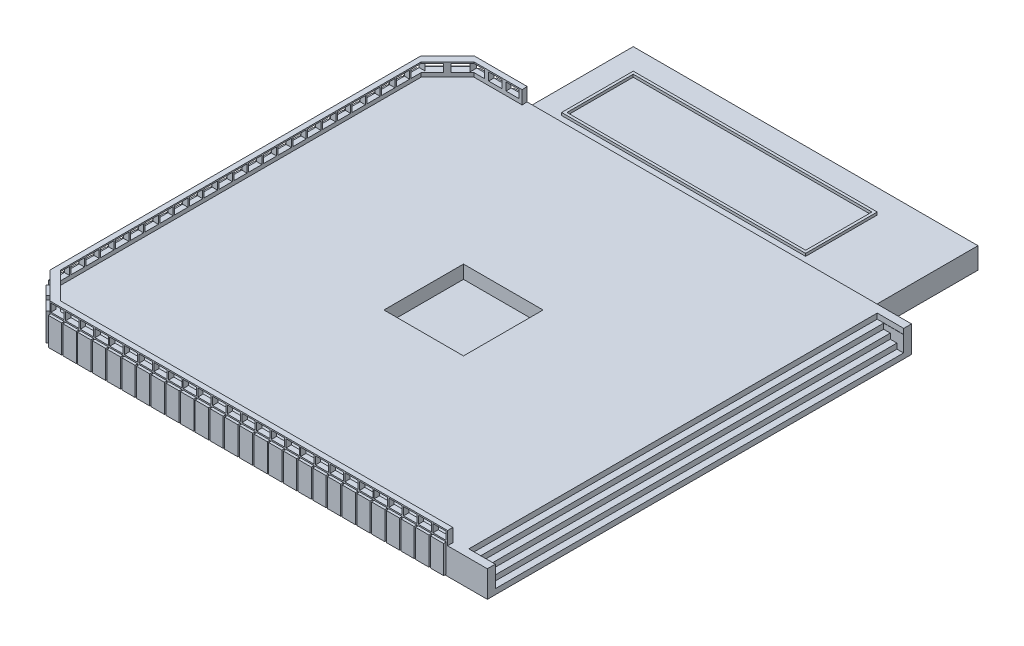
SolidWorks part; units mm, degrees
ref_plane "Front Plane" through (0, 0, 0) normal (0, 0, 1) x (1, 0, 0)
ref_plane "Top Plane" through (0, 0, 0) normal (0, 1, 0) x (1, 0, 0)
ref_plane "Right Plane" through (0, 0, 0) normal (1, 0, 0) x (0, 0, -1)
sketch "Sketch1" plane through (0, 0, 0) normal (0, 1, 0) x (1, 0, 0)
  line L0 (0, 1778) -> (0, -1778)
  line L1 (254, 2032) -> (4064, 2032)
  line L2 (254, -2032) -> (4064, -2032)
  line L3 (4064, 2032) -> (4064, -2032)
  line L4 (4064, 2032) -> (4064, 3048)
  line L5 (4064, 3048) -> (762, 3048)
  line L6 (762, 3048) -> (762, 2032)
  line L7 (0, -1778) -> (254, -2032)
  line L8 (254, 2032) -> (0, 1778)
  point P0 (0, 2032)
  point P1 (0, -2032)
  dimension "D1" = 4064
  dimension "D2" = 2032
  dimension "D3" = 4064
  dimension "D4" = 4064
  dimension "D5" = 1016
  dimension "D6" = 3302
extrude "Boss-Extrude3" add sketch "Sketch1" along normal blind 381 contours L3 L1 L0 L2 | L5 L6 L1 L4 region at (2039.6366, 0, 0) region at (2413, 0, -2540)
sketch "Sketch3" plane through (0, 381, 0) normal (0, 1, 0) x (1, 0, 0)
  line L0 (3914, 2030) -> (4064, 2030)
  line L1 (4064, 3048) -> (4064, -2032) construction
  line L2 (0, 1778) -> (0, -1778) construction
  line L3 (4064, 2030) -> (4064, -2030)
  line L4 (4064, -2030) -> (3914, -2030)
  line L5 (304.8, 1981.2) -> (765.2002, 1981.2)
  line L6 (50.8, 1727.2) -> (50.8, -1727.2)
  line L7 (304.8, -1981.2) -> (4064, -1981.2)
  line L8 (254, 2032) -> (762, 2032) construction
  line L9 (254, -2032) -> (4064, -2032) construction
  line L10 (4064, 1981.2) -> (4064, -1981.2)
  line L11 (762, 2032) -> (4064, 2030)
  line L12 (50.8, 1981.2) -> (4064, -1981.2) construction
  line L13 (50.8, -1981.2) -> (4064, 1981.2) construction
  line L14 (765.2002, 1981.2) -> (762, 2032)
  line L15 (50.8, 1727.2) -> (304.8, 1981.2)
  line L16 (50.8, -1727.2) -> (304.8, -1981.2)
  line L17 (4064, 3048) -> (762, 3048) construction
  line L18 (762, 3048) -> (4064, 3048)
  line L19 (762, 3048) -> (762, 2030)
  line L20 (762, 2030) -> (4064, 2030)
  line L21 (4064, 3048) -> (4064, 2030)
  line L22 (762, 3048) -> (4064, 2030) construction
  line L23 (762, 2030) -> (4064, 3048) construction
  line L24 (762, 3048) -> (762, 2032) construction
  point P10 (2057.4, 0)
  point P24 (2413, 2539)
  line M5 (4064, -2032) -> (4064, 3048)
  dimension "D1" = 150
  dimension "D2" = 150
  dimension "D3" = 2
  dimension "D4" = 2
  dimension "D5" = 0
  dimension "D6" = 0
  dimension "D7" = 50.8
  dimension "D8" = 50.8
  dimension "D9" = 0
extrude "Cut-Extrude10" cut sketch "Sketch3" against normal blind 127 contours L20 L14 L5 L15 L6 L16 L7 L3 L0 M5 region at (2068.7387, 381, -20.1904)
sketch "Sketch5" plane through (0, 0, 2032) normal (0, 0, 1) x (1, 0, 0)
  line L1 (3924.3, 279.4) -> (4051.3, 279.4)
  line L2 (3924.3, 279.4) -> (3924.3, 12.7)
  line L3 (3924.3, 12.7) -> (4051.3, 12.7)
  line L4 (4051.3, 279.4) -> (4051.3, 12.7)
  line L5 (3924.3, 279.4) -> (4051.3, 12.7) construction
  line L6 (3924.3, 12.7) -> (4051.3, 279.4) construction
  line L14 (4064, 381) -> (4064, 0) construction
  line L15 (254, 0) -> (4064, 0) construction
  point P0 (3987.8, 146.05)
  dimension "D1" = 12.7
  dimension "D3" = 12.7
  dimension "D5" = 127
  dimension "D6" = 266.7
sketch "Sketch6" plane through (0, 0, 2032) normal (0, 0, 1) x (1, 0, 0)
  line L0 (4064, 381) -> (4064, 0) construction
  line L1 (3924.3, 368.3) -> (4051.3, 368.3)
  line L2 (3924.3, 368.3) -> (3924.3, 292.1)
  line L3 (3924.3, 292.1) -> (4051.3, 292.1)
  line L4 (4051.3, 368.3) -> (4051.3, 292.1)
  line L5 (3924.3, 368.3) -> (4051.3, 292.1) construction
  line L6 (3924.3, 292.1) -> (4051.3, 368.3) construction
  line L7 (3924.3, 279.4) -> (4051.3, 279.4) construction
  line L8 (254, 381) -> (4064, 381) construction
  point P0 (3987.8, 330.2)
  dimension "D1" = 12.7
  dimension "D2" = 127
  dimension "D3" = 12.7
  dimension "D4" = 12.7
sketch "Sketch24" plane through (0, 381, 0) normal (0, 1, 0) x (1, 0, 0)
  line L0 (762.126, 2030) -> (4064, 2030) construction
  line L1 (762, 3048) -> (4064, 3048)
  line L2 (762, 3048) -> (762, 2030)
  line L3 (762, 2030) -> (4064, 2030)
  line L4 (4064, 3048) -> (4064, 2030)
  line L5 (762, 3048) -> (4064, 2030) construction
  line L6 (762, 2030) -> (4064, 3048) construction
  line L7 (4064, 3048) -> (4064, 2030) construction
  line L8 (762, 3048) -> (762, 2032) construction
  line L9 (4064, 3048) -> (762, 3048) construction
  point P0 (2413, 2539)
  dimension "D1" = 0
  dimension "D2" = 0
  dimension "D3" = 0
  dimension "D4" = 0
extrude "Cut-Extrude11" cut sketch "Sketch24" against normal blind 177.8
extrude "Boss-Extrude4" add sketch "Sketch5" along normal blind 25.4 contours L2 L3 L4 L1
extrude "Cut-Extrude3" cut sketch "Sketch6" against normal blind 177.8 contours L1 L4 L3 L2
pattern_linear "LPattern1" count 27 spacing 140.716 along (-1, 0, 0) of "Boss-Extrude4"
pattern_linear "LPattern2" count 27 spacing 140.716 along (-1, 0, 0) of "Cut-Extrude3"
sketch "Sketch10" plane through (0, 0, 0) normal (-1, 0, 0) x (0, 0, 1)
  line L0 (1778, 381) -> (1778, 0) construction
  line L1 (1638.3, 279.4) -> (1765.3, 279.4)
  line L2 (1638.3, 279.4) -> (1638.3, 12.7)
  line L3 (1638.3, 12.7) -> (1765.3, 12.7)
  line L4 (1765.3, 279.4) -> (1765.3, 12.7)
  line L5 (1638.3, 279.4) -> (1765.3, 12.7) construction
  line L6 (1638.3, 12.7) -> (1765.3, 279.4) construction
  line L7 (-1778, 0) -> (1778, 0) construction
  point P0 (1701.8, 146.05)
  dimension "D1" = 12.7
  dimension "D2" = 12.7
  dimension "D5" = 127
  dimension "D6" = 266.7
sketch "Sketch11" plane through (0, 0, 0) normal (-1, 0, 0) x (0, 0, 1)
  line L1 (1638.3, 368.3) -> (1765.3, 368.3)
  line L2 (1638.3, 368.3) -> (1638.3, 292.1)
  line L3 (1638.3, 292.1) -> (1765.3, 292.1)
  line L4 (1765.3, 368.3) -> (1765.3, 292.1)
  line L5 (1638.3, 368.3) -> (1765.3, 292.1) construction
  line L6 (1638.3, 292.1) -> (1765.3, 368.3) construction
  line L9 (1778, 381) -> (1778, 0) construction
  line L10 (-1778, 381) -> (1778, 381) construction
  point P0 (1701.8, 330.2)
  dimension "D1" = 12.7
  dimension "D2" = 127
  dimension "D3" = 12.7
  dimension "D4" = 76.2
extrude "Boss-Extrude5" add sketch "Sketch10" along normal blind 25.4 contours L2 L3 L4 L1
extrude "Cut-Extrude6" cut sketch "Sketch11" against normal through all contours L1 L4 L3 L2
pattern_linear "LPattern3" count 25 spacing 141.605 along (0, 0, -1) of "Cut-Extrude6"
pattern_linear "LPattern4" count 25 spacing 141.605 along (0, 0, -1) of "Boss-Extrude5"
sketch "Sketch12" plane through (0, 0, -2032) normal (0, 0, -1) x (-1, 0, 0)
  line L1 (-406.4, 368.3) -> (-279.4, 368.3)
  line L2 (-406.4, 368.3) -> (-406.4, 292.1)
  line L3 (-406.4, 292.1) -> (-279.4, 292.1)
  line L4 (-279.4, 368.3) -> (-279.4, 292.1)
  line L5 (-406.4, 368.3) -> (-279.4, 292.1) construction
  line L6 (-406.4, 292.1) -> (-279.4, 368.3) construction
  line L9 (-254, 381) -> (-254, 0) construction
  line L10 (-254, 381) -> (-762, 381) construction
  point P0 (-342.9, 330.2)
  dimension "D1" = 25.4
  dimension "D2" = 127
  dimension "D3" = 12.7
  dimension "D4" = 76.2
sketch "Sketch13" plane through (0, 0, -2032) normal (0, 0, -1) x (-1, 0, 0)
  line L0 (-254, 381) -> (-254, 0) construction
  line L1 (-406.4, 279.4) -> (-279.4, 279.4)
  line L2 (-406.4, 279.4) -> (-406.4, 12.7)
  line L3 (-406.4, 12.7) -> (-279.4, 12.7)
  line L4 (-279.4, 279.4) -> (-279.4, 12.7)
  line L5 (-406.4, 279.4) -> (-279.4, 12.7) construction
  line L6 (-406.4, 12.7) -> (-279.4, 279.4) construction
  line L7 (-254, 0) -> (-762, 0) construction
  point P0 (-342.9, 146.05)
  dimension "D2" = 12.7
  dimension "D5" = 127
  dimension "D6" = 266.7
  dimension "1" = 25.4
extrude "Boss-Extrude6" add sketch "Sketch13" along normal blind 25.4 contours L2 L3 L4 L1
extrude "Cut-Extrude7" cut sketch "Sketch12" against normal blind 177.8 contours L2 L3 L4 L1
pattern_linear "LPattern5" count 3 spacing 165.1 along (1, 0, 0) of "Boss-Extrude6", "Cut-Extrude7"
sketch "Sketch17" plane through (-889, 0, 889) normal (-0.7071, 0, 0.7071) x (0.7071, 0, 0.7071)
  line L1 (1464.0461, 279.4) -> (1591.0461, 279.4)
  line L2 (1464.0461, 279.4) -> (1464.0461, 12.7)
  line L3 (1464.0461, 12.7) -> (1591.0461, 12.7)
  line L4 (1591.0461, 279.4) -> (1591.0461, 12.7)
  line L5 (1464.0461, 279.4) -> (1591.0461, 12.7) construction
  line L6 (1464.0461, 12.7) -> (1591.0461, 279.4) construction
  line L8 (1257.2359, 0) -> (1616.4461, 0) construction
  line L9 (1616.4461, 381) -> (1616.4461, 0) construction
  point P0 (1527.5461, 146.05)
  dimension "D1" = 12.7
  dimension "D2" = 25.4
  dimension "D5" = 127
  dimension "D6" = 266.7
sketch "Sketch20" plane through (-889, 0, 889) normal (-0.7071, 0, 0.7071) x (0.7071, 0, 0.7071)
  line L0 (1257.2359, 381) -> (1616.4461, 381) construction
  line L1 (1464.0461, 368.3) -> (1591.0461, 368.3)
  line L2 (1464.0461, 368.3) -> (1464.0461, 292.1)
  line L3 (1464.0461, 292.1) -> (1591.0461, 292.1)
  line L4 (1591.0461, 368.3) -> (1591.0461, 292.1)
  line L5 (1464.0461, 368.3) -> (1591.0461, 292.1) construction
  line L6 (1464.0461, 292.1) -> (1591.0461, 368.3) construction
  line L10 (1616.4461, 381) -> (1616.4461, 0) construction
  point P0 (1527.5461, 330.2)
  dimension "D1" = 12.7
  dimension "D2" = 127
  dimension "D3" = 25.4
  dimension "D4" = 76.2
extrude "Boss-Extrude7" add sketch "Sketch17" along normal blind 25.4
extrude "Cut-Extrude8" cut sketch "Sketch20" against normal blind 177.8
pattern_linear "LPattern7" count 2 spacing 177.8 along (-0.7071, 0, -0.7071) of "Boss-Extrude7", "Cut-Extrude8"
sketch "Sketch21" plane through (-889, 0, -889) normal (-0.7071, 0, -0.7071) x (-0.7071, 0, 0.7071)
  line L0 (-1257.2359, 381) -> (-1257.2359, 0) construction
  line L1 (-1409.6359, 279.4) -> (-1282.6359, 279.4)
  line L2 (-1409.6359, 279.4) -> (-1409.6359, 12.7)
  line L3 (-1409.6359, 12.7) -> (-1282.6359, 12.7)
  line L4 (-1282.6359, 279.4) -> (-1282.6359, 12.7)
  line L5 (-1409.6359, 279.4) -> (-1282.6359, 12.7) construction
  line L6 (-1409.6359, 12.7) -> (-1282.6359, 279.4) construction
  line L7 (-1616.4461, 0) -> (-1257.2359, 0) construction
  point P0 (-1346.1359, 146.05)
  dimension "D1" = 25.4
  dimension "D2" = 12.7
  dimension "D5" = 127
  dimension "D6" = 266.7
sketch "Sketch22" plane through (-889, 0, -889) normal (-0.7071, 0, -0.7071) x (-0.7071, 0, 0.7071)
  line L1 (-1409.6359, 368.3) -> (-1282.6359, 368.3)
  line L2 (-1409.6359, 368.3) -> (-1409.6359, 292.1)
  line L3 (-1409.6359, 292.1) -> (-1282.6359, 292.1)
  line L4 (-1282.6359, 368.3) -> (-1282.6359, 292.1)
  line L5 (-1409.6359, 368.3) -> (-1282.6359, 292.1) construction
  line L6 (-1409.6359, 292.1) -> (-1282.6359, 368.3) construction
  line L7 (-1257.2359, 381) -> (-1257.2359, 0) construction
  line L8 (-1616.4461, 381) -> (-1257.2359, 381) construction
  point P0 (-1346.1359, 330.2)
  dimension "D1" = 25.4
  dimension "D2" = 127
  dimension "D3" = 12.7
  dimension "D4" = 76.2
extrude "Boss-Extrude8" add sketch "Sketch21" along normal blind 25.4 contours L1 L4 L3 L2
extrude "Cut-Extrude9" cut sketch "Sketch22" against normal blind 177.8 contours L1 L4 L3 L2
pattern_linear "LPattern8" count 2 spacing 177.8 along (0.7071, 0, -0.7071) of "Cut-Extrude9", "Boss-Extrude8"
sketch "Sketch25" plane through (0, 203.2, 0) normal (0, 1, 0) x (1, 0, 0)
  line L0 (4064, 3048) -> (762, 3048) construction
  line L1 (1016, 2794) -> (3302, 2794)
  line L2 (1016, 2794) -> (1016, 2159)
  line L3 (1016, 2159) -> (3302, 2159)
  line L4 (3302, 2794) -> (3302, 2159)
  line L5 (1016, 2794) -> (3302, 2159) construction
  line L6 (1016, 2159) -> (3302, 2794) construction
  line L7 (762, 3048) -> (762, 2032) construction
  point P0 (2159, 2476.5)
  dimension "D1" = 254
  dimension "D2" = 254
  dimension "D3" = 635
  dimension "D4" = 2286
extrude "Extrude-Thin1" add sketch "Sketch25" along normal blind 25.4 thin thin type one direction wall 25.4
sketch "Sketch26" plane through (4064, 0, 0) normal (1, 0, 0) x (0, 0, -1)
  line L0 (0, 0) -> (-2032, 0)
  line L3 (-2032, 0) -> (-2032, 254)
  line L4 (-2032, 279.4) -> (-2032, 12.7) construction
  line L5 (-2032, 254) -> (2030, 254)
  line L6 (2030, 254) -> (2032, 0)
  line L7 (2032, 0) -> (0, 0)
extrude "Boss-Extrude9" add sketch "Sketch26" along normal blind 381
sketch "Sketch27" plane through (4445, 0, 0) normal (1, 0, 0) x (0, 0, -1)
  line L0 (2030, 254) -> (-2032, 254) construction
  line L1 (-1955.8, 254) -> (1955.8, 254)
  line L2 (-1955.8, 254) -> (-1955.8, 203.2)
  line L3 (-1955.8, 203.2) -> (1955.8, 203.2)
  line L4 (1955.8, 254) -> (1955.8, 203.2)
  line L5 (-2032, 254) -> (-2032, 0) construction
  line L8 (2032, 381) -> (2032, 203.2) construction
  dimension "D1" = 76.2
  dimension "D2" = 76.2
  dimension "D3" = 50.8
extrude "Cut-Extrude12" cut sketch "Sketch27" against normal blind 254
sketch "Sketch29" plane through (4445, 0, 0) normal (1, 0, 0) x (0, 0, -1)
  line L0 (2030, 254) -> (2030, 381) construction
  line L1 (-1955.8, 203.2) -> (1953.8, 203.2)
  line L2 (-1955.8, 203.2) -> (-1955.8, 152.4)
  line L3 (-1955.8, 152.4) -> (1953.8, 152.4)
  line L4 (1953.8, 203.2) -> (1953.8, 152.4)
  dimension "D1" = 76.2
  dimension "D2" = 50.8
extrude "Cut-Extrude13" cut sketch "Sketch29" against normal blind 190.5
sketch "Sketch30" plane through (4445, 0, 0) normal (1, 0, 0) x (0, 0, -1)
  line L0 (2030, 254) -> (2030, 381) construction
  line L3 (-1955.8, 152.4) -> (1953.8, 152.4)
  line L4 (-1955.8, 152.4) -> (-1955.8, 101.6)
  line L5 (-1955.8, 101.6) -> (1953.8, 101.6)
  line L6 (1953.8, 152.4) -> (1953.8, 101.6)
  dimension "D1" = 76.2
  dimension "D2" = 50.8
extrude "Cut-Extrude14" cut sketch "Sketch30" against normal blind 127
sketch "Sketch31" plane through (4445, 0, 0) normal (1, 0, 0) x (0, 0, -1)
  line L1 (-1955.8, 101.6) -> (1953.8, 101.6)
  line L2 (-1955.8, 101.6) -> (-1955.8, 50.8)
  line L3 (-1955.8, 50.8) -> (1953.8, 50.8)
  line L4 (1953.8, 101.6) -> (1953.8, 50.8)
  line L5 (2030, 254) -> (2030, 381) construction
  dimension "D1" = 76.2
  dimension "D2" = 50.8
extrude "Cut-Extrude15" cut sketch "Sketch31" against normal blind 63.5
sketch "Sketch32" plane through (0, 254, 0) normal (0, 1, 0) x (1, 0, 0)
  line L0 (2184.4, -1981.2) -> (2184.4, 0) construction
  line L5 (304.8, -1981.2) -> (4064, -1981.2) construction
  line L6 (50.8, 0) -> (2184.4, 0) construction
  line L7 (50.8, 1727.2) -> (50.8, -1727.2) construction
  line L9 (1803.4, 381) -> (2565.4, 381)
  line L10 (1803.4, 381) -> (1803.4, -381)
  line L11 (1803.4, -381) -> (2565.4, -381)
  line L12 (2565.4, 381) -> (2565.4, -381)
  line L13 (1803.4, 381) -> (2565.4, -381) construction
  line L14 (1803.4, -381) -> (2565.4, 381) construction
  dimension "D1" = 762
  dimension "D2" = 762
extrude "Cut-Extrude16" cut sketch "Sketch32" against normal blind 127
equation "\"`\"=0.5"
